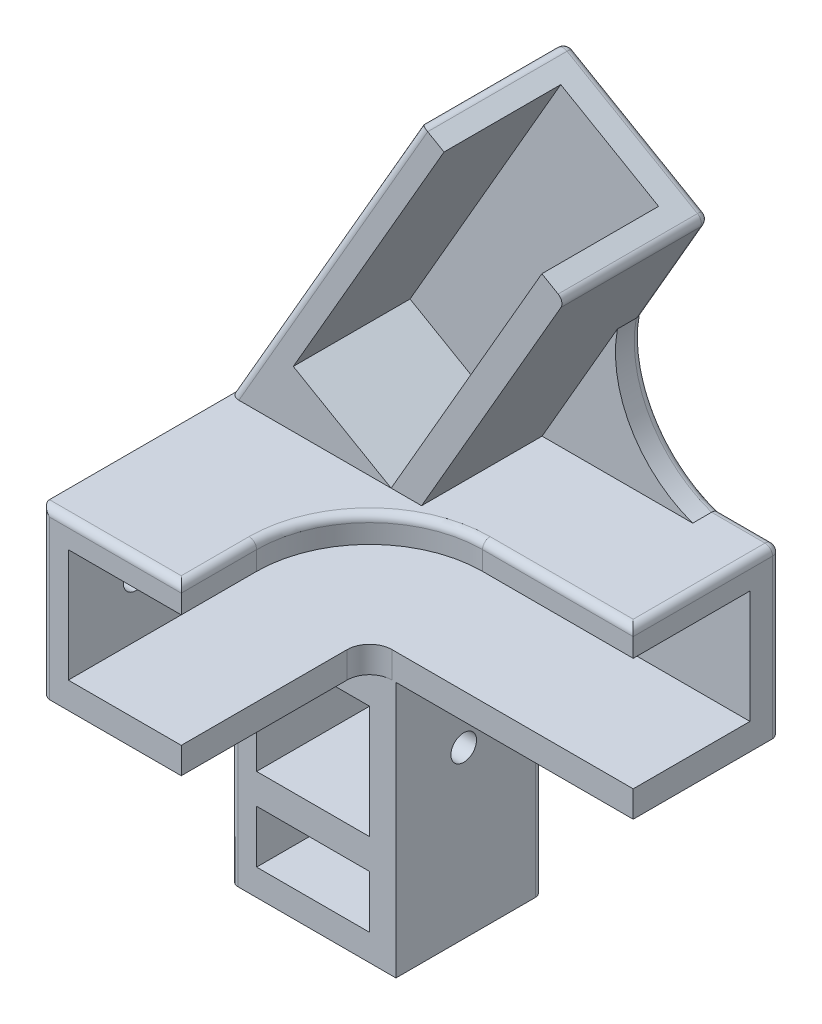
SolidWorks part; units mm, degrees
ref_plane "Front Plane" through (0, 0, 0) normal (0, 0, 1) x (1, 0, 0)
ref_plane "Top Plane" through (0, 0, 0) normal (0, 1, 0) x (1, 0, 0)
ref_plane "Right Plane" through (0, 0, 0) normal (1, 0, 0) x (0, 0, -1)
sketch "Sketch1" plane through (0, 0, 0) normal (0, 0, 1) x (1, 0, 0)
  line L1 (-5.6994, 32.9163) -> (16.3006, 32.9163)
  line L2 (-5.6994, 10.9163) -> (-5.6994, -23.0837)
  line L3 (-5.6994, -23.0837) -> (16.3006, -23.0837)
  line L4 (16.3006, 32.9163) -> (16.3006, -23.0837)
  line L5 (-5.6994, 10.9163) -> (-37.1994, 10.9163)
  line L7 (-5.6994, 32.9163) -> (-37.1994, 32.9163)
  line L8 (-37.1994, 10.9163) -> (-37.1994, 32.9163)
  dimension "D1" = 22
  dimension "D2" = 22
  dimension "D3" = 56
  dimension "D4" = 53.5
extrude "Boss-Extrude1" add sketch "Sketch1" along normal blind 19.5
sketch "Sketch3" plane through (0, 0, 19.5) normal (0, 0, 1) x (1, 0, 0)
  line L1 (16.3006, 32.9163) -> (-2.1994, 32.9163)
  line L2 (16.3006, 32.9163) -> (16.3006, 10.9163)
  line L3 (16.3006, 10.9163) -> (-2.1994, 10.9163)
  line L4 (-2.1994, 32.9163) -> (-2.1994, 10.9163)
  dimension "D1" = 18.5
extrude "Boss-Extrude2" add sketch "Sketch3" along normal blind 25
sketch "Sketch5" plane through (0, 0, 44.5) normal (0, 0, 1) x (1, 0, 0)
  line L0 (-37.1994, 32.9163) -> (-37.1994, 10.9163) construction
  line L1 (-37.1994, 29.4163) -> (12.8006, 29.4163)
  line L2 (-37.1994, 29.4163) -> (-37.1994, 14.4163)
  line L3 (-37.1994, 14.4163) -> (12.8006, 14.4163)
  line L4 (12.8006, 29.4163) -> (12.8006, 14.4163)
  line L5 (16.3006, 10.9163) -> (16.3006, 32.9163) construction
  line L6 (-2.1994, 6.4163) -> (12.8006, 6.4163)
  line L7 (-2.1994, 6.4163) -> (-2.1994, -8.5837)
  line L8 (-2.1994, -8.5837) -> (12.8006, -8.5837)
  line L9 (12.8006, 6.4163) -> (12.8006, -8.5837)
  line L12 (-2.1994, 32.9163) -> (-37.1994, 32.9163) construction
  line L13 (-2.1994, 10.9163) -> (16.3006, 10.9163) construction
  line L15 (16.3006, -23.0837) -> (16.3006, 10.9163) construction
  line L16 (-5.6994, -23.0837) -> (16.3006, -23.0837) construction
  line L17 (-2.1994, -12.5837) -> (12.8006, -12.5837)
  line L18 (-2.1994, -12.5837) -> (-2.1994, -19.5837)
  line L19 (-2.1994, -19.5837) -> (12.8006, -19.5837)
  line L20 (12.8006, -12.5837) -> (12.8006, -19.5837)
  dimension "D1" = 3.5
  dimension "D2" = 4.5
  dimension "D3" = 15
  dimension "D4" = 3.5
  dimension "D5" = 15
  dimension "D6" = 15
  dimension "D7" = 3.5
  dimension "D8" = 15
  dimension "D9" = 4
  dimension "D10" = 3.5
extrude "Cut-Extrude1" cut sketch "Sketch5" against normal offset from surface (40.5 mm away) 4 up to face at (-8.8661, 6.9163, 0)
sketch "Sketch7" plane through (16.3006, 0, 0) normal (1, 0, 0) x (0, 0, -1)
  line L0 (-34.5, 10.9163) -> (-19.5, 10.9163)
  line L1 (-44.5, 10.9163) -> (-19.5, 10.9163) construction
  line L2 (-19.5, 10.9163) -> (-19.5, -4.0837)
  line L3 (-19.5, -23.0837) -> (-19.5, 10.9163) construction
  arc A0 (-34.5, 10.9163) -> (-19.5, -4.0837) centre (-34.5, -4.0837) cw
  dimension "D1" = 15
extrude "Boss-Extrude4" add sketch "Sketch7" against normal blind 3.5
sketch "Sketch8" plane through (0, 0, 0) normal (0, 0, -1) x (-1, 0, 0)
  line L0 (5.6994, 10.9163) -> (20.6994, 10.9163)
  line L1 (37.1994, 10.9163) -> (5.6994, 10.9163) construction
  line L2 (5.6994, 10.9163) -> (5.6994, -4.0837)
  line L3 (5.6994, 10.9163) -> (5.6994, -23.0837) construction
  arc A0 (20.6994, 10.9163) -> (5.6994, -4.0837) centre (20.6994, -4.0837) ccw
  dimension "D1" = 15
extrude "Boss-Extrude5" add sketch "Sketch8" against normal blind 3.5
sketch "Sketch9" plane through (0, 32.9163, 0) normal (0, 1, 0) x (1, 0, 0)
  line L0 (-2.1994, -34.5) -> (-2.1994, -19.5)
  line L1 (-2.1994, -44.5) -> (-2.1994, -19.5) construction
  line L2 (-2.1994, -19.5) -> (-17.1994, -19.5)
  line L3 (-2.1994, -19.5) -> (-37.1994, -19.5) construction
  arc A0 (-2.1994, -34.5) -> (-17.1994, -19.5) centre (-17.1994, -34.5) ccw
  dimension "D1" = 15
extrude "Boss-Extrude6" add sketch "Sketch9" against normal blind 3.5
fillet "Fillet3" radius 3 1 edges
sketch "Sketch11" plane through (0, 0, 0) normal (0, 0, -1) x (-1, 0, 0)
  line L0 (1.1994, -23.0837) -> (1.1994, 10.9163) construction
  line L2 (5.6994, -23.0837) -> (-16.3006, -23.0837) construction
  line L5 (5.6994, -4.0837) -> (5.6994, -23.0837) construction
  text T0 "MR.3" font "Century Gothic" height 12
  dimension "D1" = 4.5
extrude "Cut-Extrude3" cut sketch "Sketch11" against normal blind 1
sketch "Sketch12" plane through (0, 0, 0) normal (0, 0, -1) x (-1, 0, 0)
  line L0 (37.1994, 21.9163) -> (-16.3006, 21.9163) construction
  line L1 (37.1994, 32.9163) -> (37.1994, 10.9163) construction
  line L2 (-16.3006, -23.0837) -> (-16.3006, 32.9163) construction
  line L3 (-12.8006, 14.4163) -> (-12.8006, 29.4163) construction
  circle A0 centre (-5.3006, 21.9163) radius 1.7
  circle A1 centre (10.9494, 21.9163) radius 1.7
  circle A2 centre (27.1994, 21.9163) radius 1.7
  dimension "D4" = 3.4
  dimension "D1" = 7.5
  dimension "D2" = 10
  dimension "D3" = 16.25
extrude "Cut-Extrude4" cut sketch "Sketch12" against normal blind 5
sketch "Sketch13" plane through (-5.6994, 0, 0) normal (-1, 0, 0) x (0, 0, 1)
  line L0 (4, 6.4163) -> (19.5, 6.4163) construction
  line L1 (19.5, 10.9163) -> (19.5, -23.0837) construction
  circle A0 centre (10.5, -1.0837) radius 1.7
  dimension "D2" = 9
  dimension "D3" = 3.4
  dimension "D1" = 7.5
extrude "Cut-Extrude5" cut sketch "Sketch13" against normal blind 45
sketch "Sketch14" plane through (16.3006, 0, 0) normal (1, 0, 0) x (0, 0, -1)
  line L0 (-10.5, -1.0837) -> (-10.5, 32.9163) construction
  line L1 (-44.5, 32.9163) -> (0, 32.9163) construction
  line L2 (-44.5, 21.9163) -> (-10.5, 21.9163) construction
  line L3 (-44.5, 10.9163) -> (-44.5, 32.9163) construction
  circle A0 centre (-10.5, 21.9163) radius 1.7
  circle A1 centre (-35.5, 21.9163) radius 1.7
  dimension "D1" = 3.4
  dimension "D2" = 9
extrude "Cut-Extrude6" cut sketch "Sketch14" against normal blind 45
sketch "Sketch15" plane through (0, -23.0837, 0) normal (0, -1, 0) x (1, 0, 0)
  line L0 (16.3006, 9.75) -> (-5.6994, 9.75) construction
  line L1 (16.3006, 19.5) -> (16.3006, 0) construction
  line L2 (-5.6994, 19.5) -> (-5.6994, 0) construction
  line L3 (5.3006, 19.5) -> (5.3006, 0) construction
  line L4 (-5.6994, 19.5) -> (16.3006, 19.5) construction
  line L5 (-5.6994, 0) -> (16.3006, 0) construction
  circle A0 centre (5.3006, 9.75) radius 1.7
  dimension "D1" = 3.4
extrude "Cut-Extrude7" cut sketch "Sketch15" against normal blind 4
mirror "Mirror2" about plane through (16.3006, 32.9163, 19.5) normal (-1, 0, 0) of "Cut-Extrude7", "Cut-Extrude6", "Cut-Extrude5", "Cut-Extrude4", "Fillet3", "Boss-Extrude6", "Boss-Extrude5", "Boss-Extrude4", "Cut-Extrude1", "Boss-Extrude2", "Boss-Extrude1"
sketch "Sketch16" plane through (0, 0, 0) normal (0, 0, -1) x (-1, 0, 0)
  line L0 (-69.8006, 32.9163) -> (37.1994, 32.9163) construction
  line L1 (-16.3006, 32.9163) -> (53.9943, 32.9163)
  line L2 (-16.3006, 32.9163) -> (-16.3006, -24.95)
  line L3 (-16.3006, -24.95) -> (53.9943, -24.95)
  line L4 (53.9943, 32.9163) -> (53.9943, -24.95)
extrude "Cut-Extrude8" cut sketch "Sketch16" against normal blind 72
sketch "Sketch20" plane through (0, 0, 0) normal (0, 0, -1) x (-1, 0, 0)
  line L0 (-20.8006, -23.0837) -> (-20.8006, 10.9163) construction
  line L1 (-16.3006, -23.0837) -> (-38.3006, -23.0837) construction
  line L2 (-16.3006, 32.9163) -> (-16.3006, -23.0837) construction
  text T0 "MR.3" font "Century Gothic" height 12
  dimension "D1" = 4.5
extrude "Cut-Extrude9" cut sketch "Sketch20" against normal blind 1
sketch "Sketch21" plane through (0, 0, 0) normal (0, 0, -1) x (-1, 0, 0)
  line L0 (-16.3006, 32.9163) -> (-41.6514, 76.8252)
  line L1 (-41.6514, 76.8252) -> (-60.704, 65.8252)
  line L2 (-60.704, 65.8252) -> (-41.704, 32.9163)
  line L3 (-69.8006, 32.9163) -> (-16.3006, 32.9163) construction
  line L4 (-41.704, 32.9163) -> (-16.3006, 32.9163)
  dimension "D1" = 22
  dimension "D2" = 60
  dimension "D3" = 38
extrude "Boss-Extrude7" add sketch "Sketch21" against normal up to surface (19.5 mm away) up to face at (57.3006, 31.1663, 19.5)
sketch "Sketch22" plane through (0, 0, 19.5) normal (0, 0, 1) x (1, 0, 0)
  line L0 (44.6825, 75.0752) -> (24.6722, 40.4163)
  line L1 (60.704, 65.8252) -> (41.6514, 76.8252) construction
  line L2 (24.6722, 40.4163) -> (37.6625, 32.9163)
  line L3 (37.6625, 32.9163) -> (57.6729, 67.5752)
  line L4 (57.6729, 67.5752) -> (44.6825, 75.0752)
  line L5 (41.6514, 76.8252) -> (16.3006, 32.9163) construction
  line L7 (16.3006, 32.9163) -> (41.704, 32.9163) construction
  dimension "D1" = 15
  dimension "D2" = 3.5
extrude "Cut-Extrude10" cut sketch "Sketch22" against normal up to surface (15.5 mm away) up to face at (41.8506, 21.9163, 4)
sketch "Sketch23" plane through (0, 0, 0) normal (0, 0, -1) x (-1, 0, 0)
  line L0 (-61.704, 32.9163) -> (-41.704, 32.9163)
  line L1 (-69.8006, 32.9163) -> (-41.704, 32.9163) construction
  line L2 (-41.704, 32.9163) -> (-51.704, 50.2368)
  line L3 (-60.704, 65.8252) -> (-41.704, 32.9163) construction
  arc A0 (-61.704, 32.9163) -> (-51.704, 50.2368) centre (-66.8048, 47.4082) ccw
  dimension "D1" = 20
extrude "Boss-Extrude8" add sketch "Sketch23" against normal blind 3.5
fillet "Fillet4" radius 1 22 edges at (16.3006, 10.9163, 39.5) (16.3006, 6.5229, 23.8934) (61.5506, 10.9163, 0) (42.694, 6.5229, 0) (34.8006, 32.9163, 39.5) (53.4997, 39.7265, 0) (28.976, 54.8707, 0) (16.3006, -13.5837, 19.5) (16.3006, 4.9163, 0) (38.3006, -13.5837, 0) (69.8006, 32.9163, 9.75) (69.8006, 21.9163, 0) (16.3006, 21.9163, 44.5) (39.194, 32.9163, 23.8934) (25.5506, 32.9163, 44.5) (41.6514, 76.8252, 9.75) (51.1777, 71.3252, 0) (60.704, 65.8252, 9.75)
